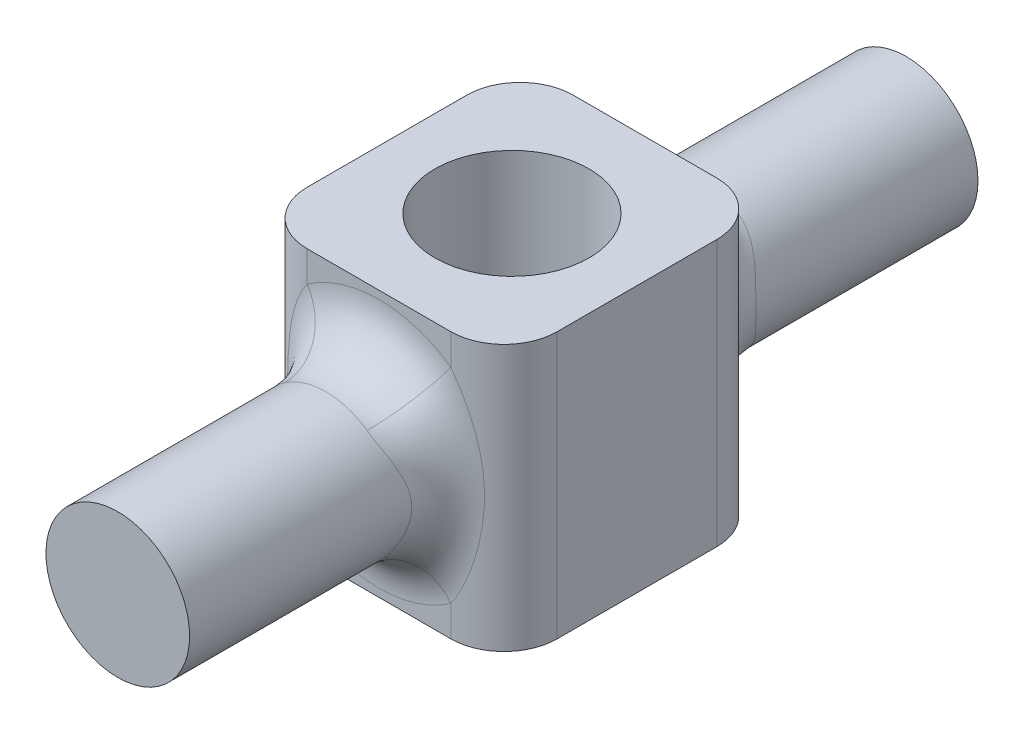
SolidWorks part; units mm, degrees
ref_plane "Front Plane" through (0, 0, 0) normal (0, 0, 1) x (1, 0, 0)
ref_plane "Top Plane" through (0, 0, 0) normal (0, 1, 0) x (1, 0, 0)
ref_plane "Right Plane" through (0, 0, 0) normal (1, 0, 0) x (0, 0, -1)
sketch "Sketch1" plane through (0, 0, 0) normal (0, 0, 1) x (1, 0, 0)
  circle A0 centre (0, 0) radius 13.5
  dimension "D1" = 27
extrude "Boss-Extrude1" add sketch "Sketch1" along normal mid plane 148.167
sketch "Sketch3" plane through (0, 0, 0) normal (0, 1, 0) x (1, 0, 0)
  line L0 (-13.5, 74.0835) -> (-13.5, -74.0835) construction
  line L1 (13.5, 15) -> (-13.5, 15)
  line L2 (13.5, 15) -> (13.5, -15)
  line L3 (13.5, -15) -> (-13.5, -15)
  line L4 (-13.5, 15) -> (-13.5, -15)
  line L5 (13.5, 15) -> (-13.5, -15) construction
  line L6 (13.5, -15) -> (-13.5, 15) construction
  line L8 (13.5006, 25) -> (-13.5006, 25)
  line L9 (23.5006, 15) -> (23.5006, -15)
  line L10 (13.5006, -25) -> (-13.5006, -25)
  line L11 (-23.5006, 15) -> (-23.5006, -15)
  line L12 (23.5006, 25) -> (-23.5006, -25) construction
  line L13 (23.5006, -25) -> (-23.5006, 25) construction
  arc A0 (-13.5006, -25) -> (-23.5006, -15) centre (-13.5006, -15) cw
  arc A1 (23.5006, -15) -> (13.5006, -25) centre (13.5006, -15) cw
  arc A2 (13.5006, 25) -> (23.5006, 15) centre (13.5006, 15) cw
  arc A3 (-13.5006, 25) -> (-23.5006, 15) centre (-13.5006, 15) ccw
  point P0 (0, 0)
  point P8 (0, 0)
  dimension "D4" = 10
  dimension "D1" = 15
  dimension "D2" = 10.0006
  dimension "D3" = 10
extrude "Boss-Extrude2" add sketch "Sketch3" along normal mid plane 50 contours L8 A3 L11 A0 L10 A1 L9 A2 L4 L1 L2 L3 | L9 A1 L10 A0 L11 A3 L8 A2 region at (20.0865, 0, -21.5858)
sketch "Sketch2" plane through (0, 0, 0) normal (0, 1, 0) x (1, 0, 0)
  circle A0 centre (0, 0) radius 14.5
  dimension "D1" = 29
extrude "Cut-Extrude1" cut sketch "Sketch2" against normal mid plane 200
fillet "Fillet2" radius 10 2 edges at (13.5, 0, 25) (13.5, 0, -25)
